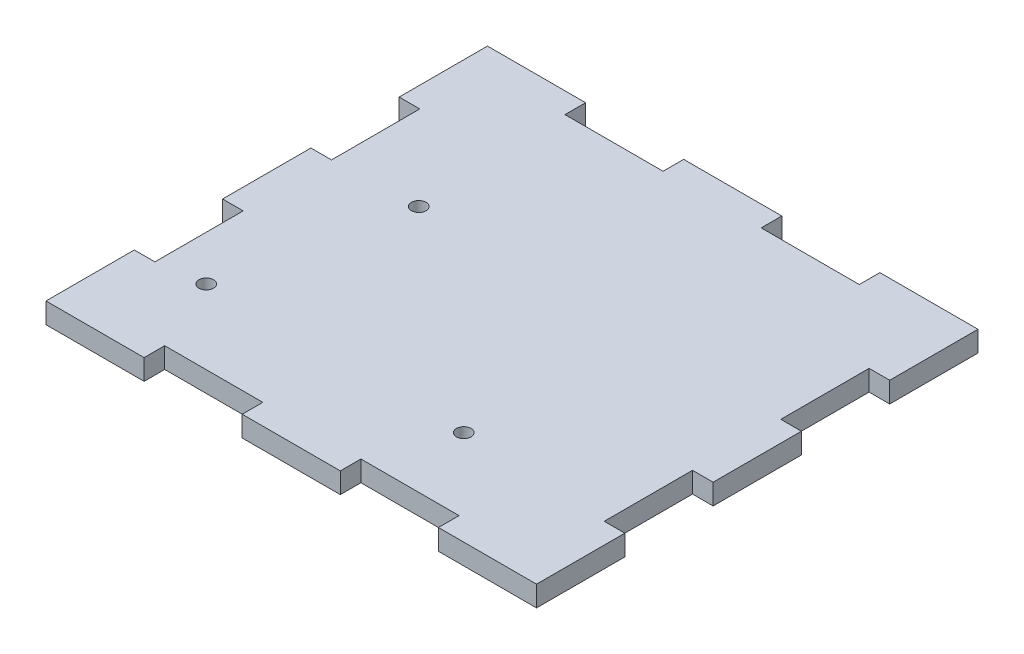
SolidWorks part; units mm, degrees
ref_plane "Front Plane" through (0, 0, 0) normal (0, 0, 1) x (1, 0, 0)
ref_plane "Top Plane" through (0, 0, 0) normal (0, 1, 0) x (1, 0, 0)
ref_plane "Right Plane" through (0, 0, 0) normal (1, 0, 0) x (0, 0, -1)
sketch "Sketch1" plane through (0, 0, 0) normal (0, 1, 0) x (1, 0, 0)
  line L1 (-63.5, -57.15) -> (63.5, -57.15)
  line L2 (-63.5, -57.15) -> (-63.5, 57.15)
  line L3 (-63.5, 57.15) -> (63.5, 57.15)
  line L4 (63.5, -57.15) -> (63.5, 57.15)
  line L5 (-63.5, -57.15) -> (63.5, 57.15) construction
  line L6 (-63.5, 57.15) -> (63.5, -57.15) construction
  point P0 (0, 0)
  dimension "D1" = 114.3
  dimension "D2" = 127
extrude "Boss-Extrude1" add sketch "Sketch1" along normal blind 5.334
sketch "Sketch2" plane through (0, 5.334, 0) normal (0, 1, 0) x (1, 0, 0)
  line L0 (-63.5, 57.15) -> (-63.5, -57.15) construction
  line L1 (-63.5, -34.29) -> (-58.166, -34.29)
  line L2 (-63.5, -34.29) -> (-63.5, -11.43)
  line L3 (-63.5, -11.43) -> (-58.166, -11.43)
  line L4 (-58.166, -34.29) -> (-58.166, -11.43)
  line L5 (63.5, 57.15) -> (-63.5, 57.15) construction
  line L6 (-63.5, 11.43) -> (-58.166, 11.43)
  line L7 (-63.5, 11.43) -> (-63.5, 34.29)
  line L8 (-63.5, 34.29) -> (-58.166, 34.29)
  line L9 (-58.166, 11.43) -> (-58.166, 34.29)
  line L10 (-38.1, 57.15) -> (-12.7, 57.15)
  line L11 (-38.1, 57.15) -> (-38.1, 51.816)
  line L12 (-38.1, 51.816) -> (-12.7, 51.816)
  line L13 (-12.7, 57.15) -> (-12.7, 51.816)
  line L14 (0, 0) -> (0, 57.15) construction
  line L15 (12.7, 57.15) -> (38.1, 57.15)
  line L16 (12.7, 57.15) -> (12.7, 51.816)
  line L17 (12.7, 51.816) -> (38.1, 51.816)
  line L18 (38.1, 57.15) -> (38.1, 51.816)
  line L19 (0, 0) -> (63.5, 0) construction
  line L20 (63.5, -57.15) -> (63.5, 57.15) construction
  line L21 (-58.166, 34.29) -> (-58.166, 57.15) construction
  line L22 (-58.166, 11.43) -> (-58.166, -11.43) construction
  line L23 (-58.166, -34.29) -> (-58.166, -57.15) construction
  line L24 (-63.5, -57.15) -> (63.5, -57.15) construction
  line L25 (-38.1, 51.816) -> (-63.5, 51.816) construction
  line L26 (-12.7, 51.816) -> (12.7, 51.816) construction
  line L27 (38.1, 51.816) -> (63.5, 51.816) construction
  line L28 (58.166, -34.29) -> (58.166, -57.15) construction
  line L29 (58.166, 11.43) -> (58.166, -11.43) construction
  line L30 (58.166, 34.29) -> (58.166, 57.15) construction
  line L31 (58.166, 11.43) -> (58.166, 34.29)
  line L32 (63.5, 34.29) -> (58.166, 34.29)
  line L33 (63.5, 11.43) -> (63.5, 34.29)
  line L34 (63.5, 11.43) -> (58.166, 11.43)
  line L35 (58.166, -34.29) -> (58.166, -11.43)
  line L36 (63.5, -11.43) -> (58.166, -11.43)
  line L37 (63.5, -34.29) -> (63.5, -11.43)
  line L38 (63.5, -34.29) -> (58.166, -34.29)
  line L39 (38.1, -51.816) -> (63.5, -51.816) construction
  line L40 (-12.7, -51.816) -> (12.7, -51.816) construction
  line L41 (-38.1, -51.816) -> (-63.5, -51.816) construction
  line L42 (38.1, -57.15) -> (38.1, -51.816)
  line L43 (12.7, -51.816) -> (38.1, -51.816)
  line L44 (12.7, -57.15) -> (12.7, -51.816)
  line L45 (12.7, -57.15) -> (38.1, -57.15)
  line L46 (-12.7, -57.15) -> (-12.7, -51.816)
  line L47 (-38.1, -51.816) -> (-12.7, -51.816)
  line L48 (-38.1, -57.15) -> (-38.1, -51.816)
  line L49 (-38.1, -57.15) -> (-12.7, -57.15)
extrude "Cut-Extrude1" cut sketch "Sketch2" against normal through all
sketch "Sketch3" plane through (0, 5.334, 0) normal (0, 1, 0) x (1, 0, 0)
  circle A0 centre (-46.5683, -32.6007) radius 1.8986 construction
  circle A1 centre (20.1067, -32.6007) radius 1.8986 construction
  circle A2 centre (-46.5683, -32.6007) radius 1.8986
  circle A3 centre (20.1067, -32.6007) radius 1.8986
extrude "Cut-Extrude2" cut sketch "Sketch3" against normal through all
sketch "Sketch4" plane through (0, 0, 0) normal (0, -1, 0) x (1, 0, 0)
  circle A0 centre (-36.4083, -12.2807) radius 1.8986 construction
  circle A1 centre (-36.4083, -12.2807) radius 1.8986
extrude "Cut-Extrude3" cut sketch "Sketch4" against normal through all
equation "\"D1@Boss-Extrude1\" = \"material\""
equation "\"material\"=\"GMaterial@Platform.assembly\""
